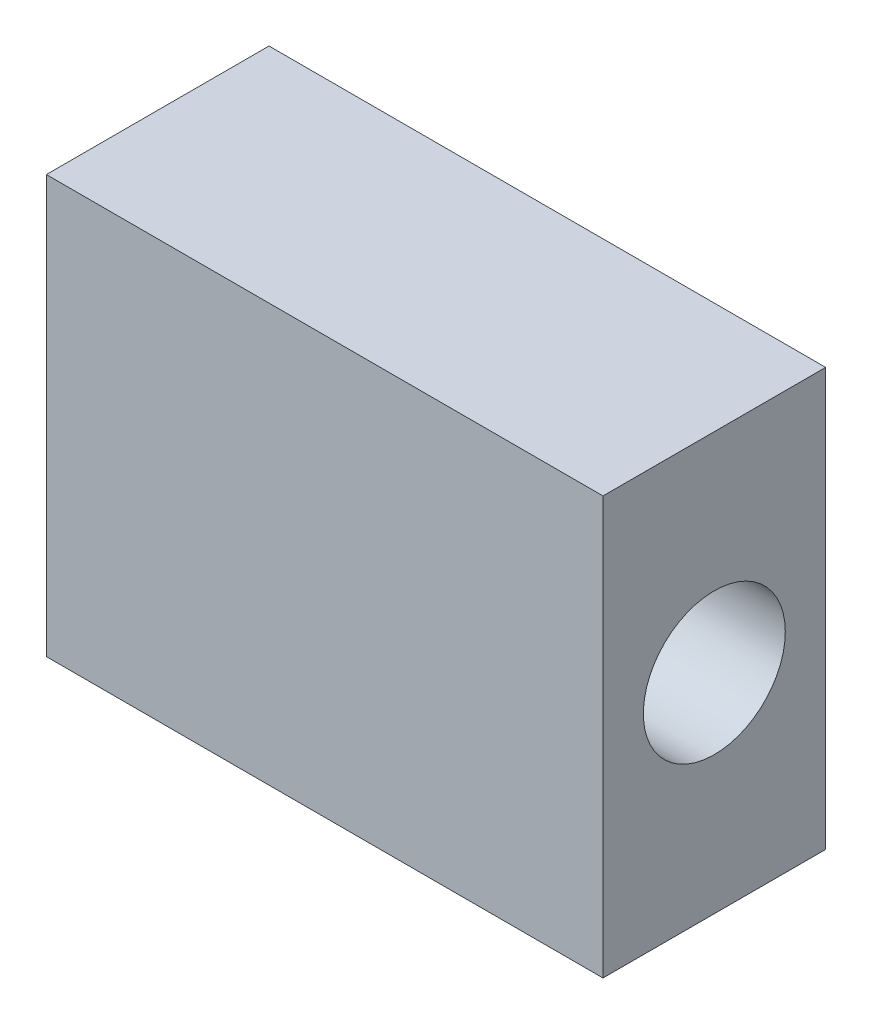
SolidWorks part; units mm, degrees
ref_plane "Alzado" through (0, 0, 0) normal (0, 0, 1) x (1, 0, 0)
ref_plane "Planta" through (0, 0, 0) normal (0, 1, 0) x (1, 0, 0)
ref_plane "Vista lateral" through (0, 0, 0) normal (1, 0, 0) x (0, 0, -1)
sketch "Croquis1" plane through (0, 0, 0) normal (0, 0, 1) x (1, 0, 0)
  line L1 (0, 0) -> (40, 0)
  line L2 (0, 0) -> (0, 30)
  line L3 (0, 30) -> (40, 30)
  line L4 (40, 0) -> (40, 30)
  dimension "D1" = 30
  dimension "D2" = 40
extrude "Saliente-Extruir1" add sketch "Croquis1" along normal blind 16
sketch "Croquis2" plane through (40, 0, 0) normal (1, 0, 0) x (0, 0, -1)
  line L0 (0, 0) -> (0, 30) construction
  line L1 (-16, 0) -> (0, 0) construction
  circle A0 centre (-8, 15) radius 5.1
  dimension "D1" = 10.2
  dimension "D2" = 8
  dimension "D3" = 15
extrude "Cortar-Extruir1" cut sketch "Croquis2" against normal through all
